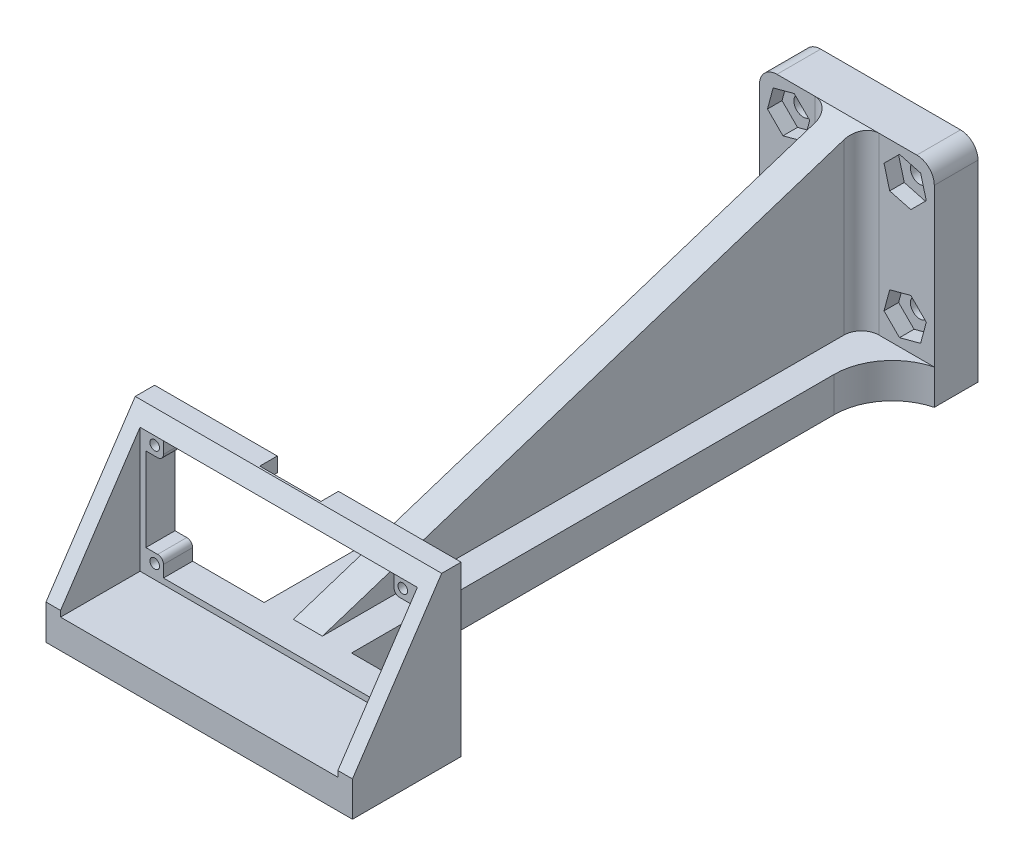
SolidWorks part; units mm, degrees
ref_plane "Plan de face" through (0, 0, 0) normal (0, 0, 1) x (1, 0, 0)
ref_plane "Plan de dessus" through (0, 0, 0) normal (0, 1, 0) x (1, 0, 0)
ref_plane "Plan de droite" through (0, 0, 0) normal (1, 0, 0) x (0, 0, -1)
sketch "Esquisse1" plane through (0, 0, 0) normal (0, 0, 1) x (1, 0, 0)
  line L1 (-21.285, -8.79) -> (21.285, -8.79) construction
  line L2 (-21.285, -8.79) -> (-21.285, 8.79) construction
  line L3 (-21.285, 8.79) -> (21.285, 8.79) construction
  line L4 (21.285, -8.79) -> (21.285, 8.79) construction
  line L5 (-21.285, -8.79) -> (21.285, 8.79) construction
  line L6 (-21.285, 8.79) -> (21.285, -8.79) construction
  line L7 (-22.795, -10.2) -> (22.795, -10.2)
  line L8 (-22.795, -10.2) -> (-22.795, 10.2)
  line L9 (-22.795, 10.2) -> (22.795, 10.2)
  line L10 (22.795, -10.2) -> (22.795, 10.2)
  line L11 (-22.795, -10.2) -> (22.795, 10.2) construction
  line L12 (-22.795, 10.2) -> (22.795, -10.2) construction
  circle A0 centre (-21.285, 8.79) radius 0.825
  circle A1 centre (21.285, 8.79) radius 0.825
  circle A2 centre (21.285, -8.79) radius 0.825
  circle A3 centre (-21.285, -8.79) radius 0.825
  point P0 (0, 0)
  point P6 (0, 0)
  dimension "D5" = 1.65
  dimension "D1" = 42.57
  dimension "D2" = 17.58
  dimension "D3" = 20.4
  dimension "D4" = 45.59
extrude "Boss.-Extru.1" add sketch "Esquisse1" along normal blind 5
sketch "Esquisse2" plane through (0, -10.2, 0) normal (0, -1, 0) x (1, 0, 0)
  line L0 (-22.795, 5) -> (22.795, 5) construction
  line L1 (-22.795, 0) -> (22.795, 0)
  line L2 (-22.795, 0) -> (-22.795, 18.64)
  line L3 (-22.795, 18.64) -> (22.795, 18.64)
  line L4 (22.795, 0) -> (22.795, 18.64)
  dimension "D1" = 13.64
extrude "Boss.-Extru.2" add sketch "Esquisse2" along normal blind 6
sketch "Esquisse3" plane through (0, -10.2, 0) normal (0, 1, 0) x (1, 0, 0)
  line L0 (22.795, -5) -> (22.795, -18.64) construction
  line L1 (-22.795, -18.64) -> (22.795, -18.64) construction
  line L2 (-22.795, -18.64) -> (-22.795, -6.64) construction
  line L3 (-22.795, -6.64) -> (22.795, -6.64) construction
  line L4 (22.795, -18.64) -> (22.795, -6.64) construction
  line L5 (-22.795, -6.64) -> (22.795, -18.64) construction
  circle A0 centre (0, -12.64) radius 1
  dimension "D2" = 2
  dimension "D1" = 12
extrude "Enlèv. mat.-Extru.1" cut sketch "Esquisse3" against normal blind 6
sketch "Esquisse4" plane through (0, -10.2, 0) normal (0, 1, 0) x (1, 0, 0)
  line L0 (22.795, -18.64) -> (-22.795, -18.64) construction
  line L1 (1.6166, -15.44) -> (3.2332, -12.64)
  line L2 (3.2332, -12.64) -> (1.6166, -9.84)
  line L3 (1.6166, -9.84) -> (-1.6166, -9.84)
  line L4 (-1.6166, -9.84) -> (-3.2332, -12.64)
  line L5 (-3.2332, -12.64) -> (-1.6166, -15.44)
  line L6 (-1.6166, -15.44) -> (1.6166, -15.44)
  circle A0 centre (0, -12.64) radius 2.8 construction
  dimension "D1" = 5.6
extrude "Enlèv. mat.-Extru.2" cut sketch "Esquisse4" against normal blind 3.5
sketch "Esquisse5" plane through (0, 0, 0) normal (0, 0, -1) x (-1, 0, 0)
  line L0 (-22.795, 10.2) -> (22.795, 10.2) construction
  line L1 (-19.775, 10.2) -> (19.775, 10.2)
  line L2 (-19.775, 10.2) -> (-19.775, -10.2)
  line L3 (-19.775, -10.2) -> (19.775, -10.2)
  line L4 (19.775, 10.2) -> (19.775, -10.2)
  line L6 (-22.795, 10.2) -> (-19.775, 10.2) construction
  line L9 (1.6166, -10.2) -> (-1.6166, -10.2) construction
  point P8 (0, 10.2)
  point P11 (-21.285, 8.79)
  point P13 (-21.285, 10.2)
extrude "Enlèv. mat.-Extru.3" cut sketch "Esquisse5" against normal blind 5
sketch "Esquisse6" plane through (-22.795, 0, 0) normal (-1, 0, 0) x (0, 0, 1)
  line L0 (0, 10.2) -> (5, 10.2)
  line L1 (5, 10.2) -> (18.64, -10.2)
  line L2 (18.64, -10.2) -> (18.64, -16.2)
  line L3 (18.64, -16.2) -> (0, -16.2)
  line L4 (0, -16.2) -> (0, 10.2)
extrude "Boss.-Extru.3" add sketch "Esquisse6" along normal blind 3.5
sketch "Esquisse7" plane through (22.795, 0, 0) normal (1, 0, 0) x (0, 0, -1)
  line L0 (0, 10.2) -> (-5, 10.2)
  line L1 (-5, 10.2) -> (-18.64, -10.2)
  line L2 (-18.64, -10.2) -> (-18.64, -16.2)
  line L3 (-18.64, -16.2) -> (0, -16.2)
  line L4 (0, -16.2) -> (0, 10.2)
extrude "Boss.-Extru.4" add sketch "Esquisse7" along normal blind 3.5
sketch "Esquisse8" plane through (0, 0, 0) normal (0, 0, -1) x (-1, 0, 0)
  line L0 (-22.795, -10.2) -> (-22.795, 10.2) construction
  line L1 (-22.795, 7.18) -> (22.795, 7.18)
  line L2 (-22.795, 7.18) -> (-22.795, -7.18)
  line L3 (-22.795, -7.18) -> (22.795, -7.18)
  line L4 (22.795, 7.18) -> (22.795, -7.18)
  line L5 (22.795, -10.2) -> (22.795, 10.2) construction
  line L6 (-20.7479, 7.18) -> (-20.7479, 10.2) construction
  line L7 (-26.295, 10.2) -> (-19.775, 10.2) construction
  line L8 (-22.795, 6.897) -> (-19.775, 6.897) construction
  line L9 (-19.775, 10.2) -> (-19.775, -10.2) construction
  line L10 (-18.5049, -10.2) -> (-18.5049, -7.18) construction
  line L11 (-19.775, -10.2) -> (19.775, -10.2) construction
extrude "Enlèv. mat.-Extru.4" cut sketch "Esquisse8" against normal blind 5
sketch "Esquisse10" plane through (22.795, 0, 0) normal (-1, 0, 0) x (0, 0, 1)
  line L0 (5, 10.2) -> (18.64, -10.2)
  line L1 (18.64, -10.2) -> (5, -10.2)
  line L2 (5, -10.2) -> (5, 10.2)
extrude "Enlèv. mat.-Extru.5" cut sketch "Esquisse10" against normal blind 1
sketch "Esquisse11" plane through (-22.795, 0, 0) normal (1, 0, 0) x (0, 0, -1)
  line L0 (-5, 10.2) -> (-18.64, -10.2)
  line L1 (-18.64, -10.2) -> (-5, -10.2)
  line L2 (-5, -10.2) -> (-5, 10.2)
extrude "Enlèv. mat.-Extru.6" cut sketch "Esquisse11" against normal blind 1
sketch "Esquisse12" plane through (0, -10.2, 0) normal (0, 1, 0) x (1, 0, 0)
  line L1 (-23.795, -5) -> (23.795, -5)
  line L2 (-23.795, -5) -> (-23.795, -18.64)
  line L3 (-23.795, -18.64) -> (23.795, -18.64)
  line L4 (23.795, -5) -> (23.795, -18.64)
extrude "Enlèv. mat.-Extru.7" cut sketch "Esquisse12" against normal blind 1
fillet "Congé2" radius 1 4 edges at (19.775, 7.18, 2.5) (19.775, -7.18, 2.5) (-19.775, -7.18, 2.5) (-19.775, 7.18, 2.5)
sketch "Esquisse13" plane through (0, 10.2, 0) normal (0, 1, 0) x (1, 0, 0)
  line L1 (-26.295, -5) -> (26.295, -5)
  line L2 (-26.295, -5) -> (-26.295, 0)
  line L3 (-26.295, 0) -> (26.295, 0)
  line L4 (26.295, -5) -> (26.295, 0)
extrude "Boss.-Extru.5" add sketch "Esquisse13" along normal blind 2.5
sketch "Esquisse14" plane through (-26.295, 0, 0) normal (-1, 0, 0) x (0, 0, 1)
  line L0 (5, 10.2) -> (2.5, 13.939)
  line L1 (2.5, 13.939) -> (5, 13.939)
  line L2 (5, 12.7) -> (5, 10.2) construction
  line L3 (5, 13.939) -> (5, 10.2)
  line L4 (18.64, -10.2) -> (5, 10.2) construction
  dimension "D1" = 2.5
extrude "Enlèv. mat.-Extru.8" cut sketch "Esquisse14" against normal blind 53.5
sketch "Esquisse15" plane through (0, -16.2, 0) normal (0, -1, 0) x (-1, 0, 0)
  circle A0 centre (0, -12.64) radius 29.1753 construction
sketch "Esquisse16" plane through (0, 0, 0) normal (0, 0, -1) x (-1, 0, 0)
  line L0 (-19.775, -10.2) -> (19.775, -10.2) construction
  line L1 (-7.5, -10.2) -> (7.5, -10.2)
  line L2 (-7.5, -10.2) -> (-7.5, -16.2)
  line L3 (-7.5, -16.2) -> (7.5, -16.2)
  line L4 (7.5, -10.2) -> (7.5, -16.2)
  line L5 (-29.1753, -16.2) -> (29.1753, -16.2) construction
  point P8 (0, -16.2)
  dimension "D1" = 15
extrude "Boss.-Extru.6" add sketch "Esquisse16" along normal blind 100
sketch "Esquisse17" plane through (0, 0, -100) normal (0, 0, -1) x (-1, 0, 0)
  line L0 (-29.1753, -16.2) -> (29.1753, -16.2) construction
  line L1 (-15, -16.2) -> (15, -16.2)
  line L2 (-15, -16.2) -> (-15, 19.8)
  line L3 (-15, 19.8) -> (15, 19.8)
  line L4 (15, -16.2) -> (15, 19.8)
  line L5 (7.5, -10.2) -> (-7.5, -10.2) construction
  line L6 (-10, 14.8) -> (10, 14.8) construction
  line L7 (-10, 14.8) -> (-10, -5.2) construction
  line L8 (-10, -5.2) -> (10, -5.2) construction
  line L9 (10, 14.8) -> (10, -5.2) construction
  line L10 (-10, 14.8) -> (10, -5.2) construction
  line L11 (-10, -5.2) -> (10, 14.8) construction
  circle A0 centre (-10, 14.8) radius 1.6
  circle A1 centre (10, 14.8) radius 1.6
  circle A2 centre (10, -5.2) radius 1.6
  circle A3 centre (-10, -5.2) radius 1.6
  point P6 (0, 19.8)
  point P8 (0, 4.8)
  point P25 (0, -5.2)
  dimension "D2" = 3.2
  dimension "D1" = 20
  dimension "D3" = 5
  dimension "D4" = 5
  dimension "D5" = 5
extrude "Boss.-Extru.7" add sketch "Esquisse17" against normal blind 7.5
sketch "Esquisse19" plane through (-7.5, 0, 0) normal (-1, 0, 0) x (0, 0, 1)
  line L0 (0, -10.2) -> (-92.5, 19.8)
  line L1 (-92.5, 19.8) -> (-92.5, -10.2)
  line L2 (-92.5, -10.2) -> (0, -10.2)
extrude "Boss.-Extru.9" add sketch "Esquisse19" against normal blind 5 from offset 5 offset against normal yes
fillet "Congé3" radius 10 2 edges at (7.5, -13.2, -92.5) (-7.5, -13.2, -92.5)
fillet "Congé4" radius 3 2 edges at (2.5, 4.8, -92.5) (-2.5, 4.8, -92.5)
fillet "Congé5" radius 3 2 edges at (15, 19.8, -96.25) (-15, 19.8, -96.25)
sketch "Esquisse20" plane through (0, 0, -92.5) normal (0, 0, 1) x (1, 0, 0)
  line L1 (-22.0691, -17.2691) -> (22.0691, -17.2691) construction
  line L2 (-22.0691, -17.2691) -> (-22.0691, 26.8691) construction
  line L3 (-22.0691, 26.8691) -> (22.0691, 26.8691) construction
  line L4 (22.0691, -17.2691) -> (22.0691, 26.8691) construction
  line L5 (-22.0691, -17.2691) -> (22.0691, 26.8691) construction
  line L6 (-22.0691, 26.8691) -> (22.0691, -17.2691) construction
  line L7 (-12.6536, 17.4536) -> (-13.6249, 13.8287)
  line L8 (-13.6249, 13.8287) -> (-10.9713, 11.1751)
  line L9 (-10.9713, 11.1751) -> (-7.3464, 12.1464)
  line L10 (-7.3464, 12.1464) -> (-6.3751, 15.7713)
  line L11 (-6.3751, 15.7713) -> (-9.0287, 18.4249)
  line L12 (-9.0287, 18.4249) -> (-12.6536, 17.4536)
  line L13 (12.6536, 17.4536) -> (9.0287, 18.4249)
  line L14 (9.0287, 18.4249) -> (6.3751, 15.7713)
  line L15 (6.3751, 15.7713) -> (7.3464, 12.1464)
  line L16 (7.3464, 12.1464) -> (10.9713, 11.1751)
  line L17 (10.9713, 11.1751) -> (13.6249, 13.8287)
  line L18 (13.6249, 13.8287) -> (12.6536, 17.4536)
  line L19 (12.6536, -7.8536) -> (13.6249, -4.2287)
  line L20 (13.6249, -4.2287) -> (10.9713, -1.5751)
  line L21 (10.9713, -1.5751) -> (7.3464, -2.5464)
  line L22 (7.3464, -2.5464) -> (6.3751, -6.1713)
  line L23 (6.3751, -6.1713) -> (9.0287, -8.8249)
  line L24 (9.0287, -8.8249) -> (12.6536, -7.8536)
  line L25 (-12.6536, -7.8536) -> (-9.0287, -8.8249)
  line L26 (-9.0287, -8.8249) -> (-6.3751, -6.1713)
  line L27 (-6.3751, -6.1713) -> (-7.3464, -2.5464)
  line L28 (-7.3464, -2.5464) -> (-10.9713, -1.5751)
  line L29 (-10.9713, -1.5751) -> (-13.6249, -4.2287)
  line L30 (-13.6249, -4.2287) -> (-12.6536, -7.8536)
  arc A0 (-12, 19.8) -> (-15, 16.8) centre (-12, 16.8) ccw construction
  arc A1 (15, 16.8) -> (12, 19.8) centre (12, 16.8) ccw construction
  circle A2 centre (-10, 14.8) radius 3.25 construction
  circle A3 centre (10, 14.8) radius 3.25 construction
  circle A4 centre (10, -5.2) radius 3.25 construction
  circle A5 centre (-10, -5.2) radius 3.25 construction
  point P0 (0, 4.8)
  point P10 (-14.1213, 18.9213)
  point P15 (14.1213, 18.9213)
  dimension "D1" = 6.5
extrude "Enlèv. mat.-Extru.9" cut sketch "Esquisse20" against normal blind 2.5
sketch "Esquisse21" plane through (0, -11.2, 0) normal (0, 1, 0) x (1, 0, 0)
  line L1 (-4.4859, -8.0504) -> (4.4859, -8.0504)
  line L2 (-4.4859, -8.0504) -> (-4.4859, -17.2296)
  line L3 (-4.4859, -17.2296) -> (4.4859, -17.2296)
  line L4 (4.4859, -8.0504) -> (4.4859, -17.2296)
  line L5 (-4.4859, -8.0504) -> (4.4859, -17.2296) construction
  line L6 (-4.4859, -17.2296) -> (4.4859, -8.0504) construction
  point P0 (0, -12.64)
extrude "Boss.-Extru.10" add sketch "Esquisse21" against normal blind 5
sketch "Esquisse22" plane through (0, -10.2, 0) normal (0, 1, 0) x (1, 0, 0)
  line L0 (26.295, 0) -> (-26.295, 0) construction
  line L1 (5.25, -3) -> (-5.25, -3)
  line L2 (5.25, -3) -> (5.25, 0)
  line L3 (5.25, 0) -> (-5.25, 0)
  line L4 (-5.25, -3) -> (-5.25, 0)
  line L5 (5.25, -3) -> (-5.25, 0) construction
  line L6 (5.25, 0) -> (-5.25, -3) construction
  point P0 (0, -1.5)
  dimension "D1" = 10.5
  dimension "D2" = 3
extrude "Enlèv. mat.-Extru.10" cut sketch "Esquisse22" along normal blind 24
sketch "Esquisse23" plane through (0, 0, 5) normal (0, 0, 1) x (1, 0, 0)
  line L2 (-23.795, -10.2) -> (23.795, -10.2)
  line L3 (-23.795, -10.2) -> (-23.795, 10.2)
  line L4 (-23.795, 10.2) -> (23.795, 10.2)
  line L5 (23.795, -10.2) -> (23.795, 10.2)
